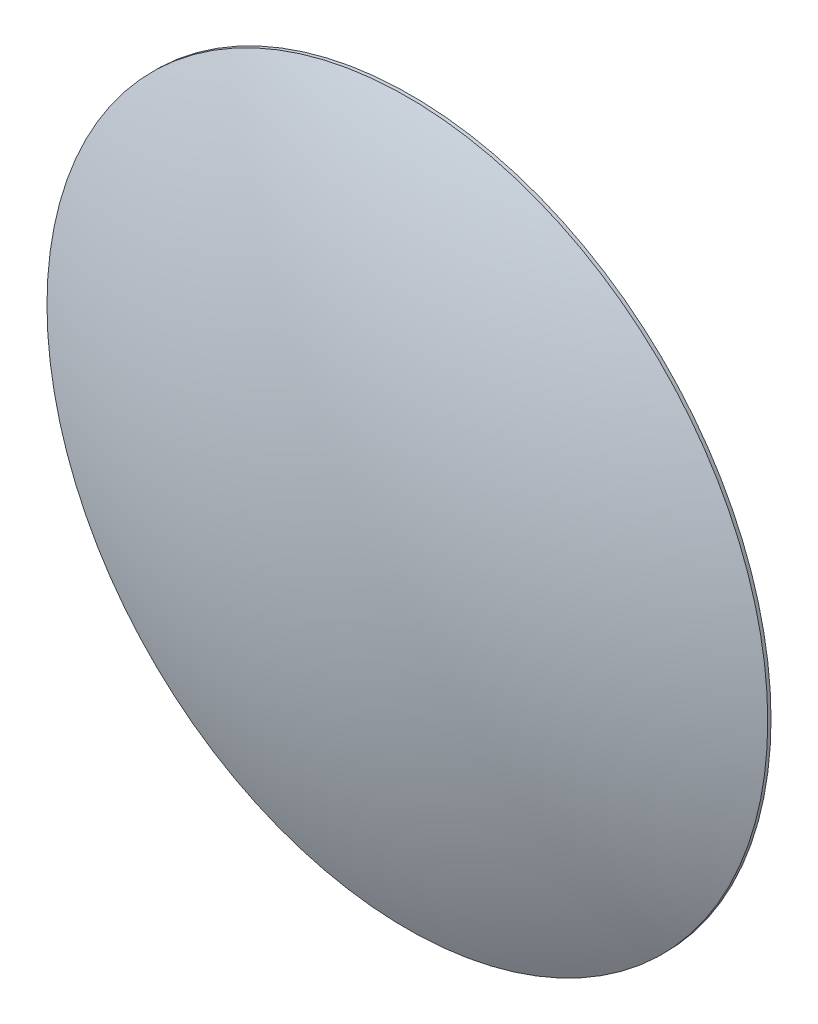
SolidWorks part; units mm, degrees
ref_plane "Face" through (0, 0, 0) normal (0, 0, 1) x (1, 0, 0)
ref_plane "Dessus" through (0, 0, 0) normal (0, 1, 0) x (1, 0, 0)
ref_plane "Droite" through (0, 0, 0) normal (1, 0, 0) x (0, 0, -1)
sketch "Esquisse1" plane through (0, 0, 0) normal (0, 0, 1) x (1, 0, 0)
  circle A0 centre (0, 0) radius 11
  dimension "D1" = 22
extrude "Extrusion2" add sketch "Esquisse1" along normal blind 0.1
dome "Dôme2" faces to dome 1 distance 2.4 reverse direction no elliptical dome no face at (11, 0, 0.1) parameters "D1"=2.4
